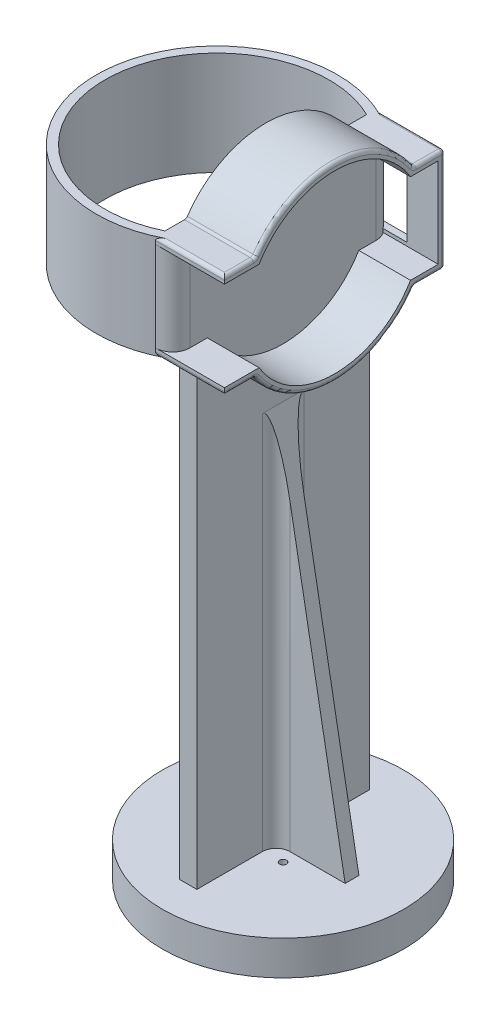
SolidWorks part; units mm, degrees
note: '?' marks a value the reader was unsure of.
ref_plane "Alzado" through (0, 0, 0) normal (0, 0, 1) x (1, 0, 0)
ref_plane "Planta" through (0, 0, 0) normal (0, 1, 0) x (1, 0, 0)
ref_plane "Vista lateral" through (0, 0, 0) normal (1, 0, 0) x (0, 0, -1)
sketch "Croquis1" plane through (0, 0, 0) normal (0, 1, 0) x (1, 0, 0)
  line L0 (0, -55) -> (0, 55) construction
  circle A0 centre (0, 0) radius 35
  point P5 (1.0317, 1.5992)
  dimension "D1" = 70
extrude "Saliente-Extruir1" add sketch "Croquis1" along normal blind 10
ref_plane "Plano1" through (0, 0, 0) normal (1, 0, 0) x (0, 0, -1)
sketch "Croquis4" plane through (0, 0, 0) normal (1, 0, 0) x (0, 0, -1)
  line L1 (-25, 10) -> (25, 10)
  line L2 (-25, 10) -> (-25, 160)
  line L3 (-25, 160) -> (25, 160)
  line L4 (25, 10) -> (25, 160)
  line L5 (35, 10) -> (-35, 10) construction
  dimension "D1" = 150
  dimension "D2" = 50
  dimension "D3" = 25
extrude "Saliente-Extruir3" add sketch "Croquis4" against normal blind 5
sketch "Croquis5" plane through (0, 0, 0) normal (1, 0, 0) x (0, 0, -1)
  line L0 (25, 160) -> (-25, 160) construction
  line L2 (-32, 145) -> (-23, 145)
  line L3 (-32, 145) -> (-32, 175)
  line L4 (-32, 175) -> (-23, 175)
  line L5 (-23, 145) -> (-23, 175)
  line L7 (23, 175) -> (32, 175)
  line L8 (23, 175) -> (23, 145)
  line L9 (23, 145) -> (32, 145)
  line L10 (32, 175) -> (32, 145)
  circle A0 centre (0, 160) radius 27.5
  line M10 (-25, 160) -> (-25, 10)
  line M12 (25, 10) -> (25, 160)
  line M13 (25, 160) -> (-25, 160)
  dimension "D1" = 55
  dimension "D2" = 30
  dimension "D3" = 9
  dimension "D4" = 32
  dimension "D5" = 15
  dimension "D6" = 30
  dimension "D7" = 9
  dimension "D8" = 15
  dimension "D9" = 32
extrude "Saliente-Extruir4" add sketch "Croquis5" along normal blind 15 and the other way blind 5 contours A0 L9 L10 L7 M12 | A0 L7 L8 M12 M13 | L9 A0 L8 M12 M13 | L2 A0 L9 L8 L5 M13 | L7 A0 L4 L5 L8 M13 | L4 A0 L5 M10 M13 | A0 L2 L5 M10 M13 | A0 L4 L3 L2 M10 | A0 L2 M10 | A0 L9 M12
sketch3d "Croquis3D1"
  line L0 (15, 173, 21.9642) -> (15, 173, 30)
  line L1 (15, 173, 30) -> (15, 147, 30)
  line L2 (15, 147, 30) -> (15, 147, 21.9642)
  line L3 (15, 147, -21.9642) -> (15, 147, -30)
  line L4 (15, 147, -30) -> (15, 173, -30)
  line L5 (15, 173, -30) -> (15, 173, -21.9642)
  line L6 (15, 173, 21.9642) -> (15, 173, 30)
  line L8 (15, 147, 30) -> (15, 147, 21.9642)
  line L9 (15, 147, -21.9642) -> (15, 147, -30)
  line L10 (15, 147, -30) -> (15, 173, -30)
  line L11 (15, 173, -30) -> (15, 173, -21.9642)
  line L12 (15, 173, 30) -> (15, 173, 32)
  line L13 (15, 145, 32) -> (15, 175, 32) construction
  line L14 (15, 173, 32) -> (15, 147, 32)
  line L15 (15, 147, 32) -> (15, 147, 30)
  line L16 (15, 145, 32) -> (15, 145, 23.0489) construction
  spline S0 degree 5 poles (15, 875.3742, 620.8936) (15, 862.2104, 487.3237) (15, 683.0793, 370.8401) (15, 504.0832, 254.3509) (15, 324.838, 137.6997) (15, 145.5929, 21.0484) (15, 145.3451, 20.8845) (15, 144.6096, 20.3812) (15, 143.9088, 19.8266) (15, 143.4553, 19.4384) (15, 142.3513, 18.433) (15, 141.3105, 17.3675) (15, 140.7119, 16.7053) (15, 139.5732, 15.3328) (15, 138.564, 13.8588) (15, 138.0925, 13.0991) (15, 137.2173, 11.54) (15, 136.4806, 9.9121) (15, 136.1479, 9.0829) (15, 135.5556, 7.3976) (15, 135.1135, 5.6665) (15, 134.9304, 4.7918) (15, 134.6411, 3.0285) (15, 134.5071, 1.2468) (15, 134.4791, 0.3536) (15, 134.5011, -1.4329) (15, 134.6794, -3.2106) (15, 134.8074, -4.095) (15, 135.1401, -5.8505) (15, 135.625, -7.5703) (15, 135.9049, -8.419) (15, 136.5382, -10.0897) (15, 137.3159, -11.6979) (15, 137.7395, -12.4846) (15, 138.6538, -14.0197) (15, 139.6972, -15.4713) (15, 140.2504, -16.1735) (15, 141.2939, -17.3806) (15, 142.4337, -18.4948) (15, 142.9519, -18.9683) (15, 143.791, -19.6898) (15, 144.66, -20.3747) (15, 144.9825, -20.6185) (15, 145.3974, -20.9162) (15, 145.823, -21.1979) (15, 145.9122, -21.2563) (15, 314.1545, -130.7469) (15, 482.3968, -240.2376) (15, 650.5497, -349.67) (15, 818.7438, -459.113) (15, 990.3967, -547.1852) knots -20.205741 -20.205741 -20.205741 -20.205741 -20.205741 -20.205741 0.020545 0.020545 0.020545 0.048685 0.048685 0.048685 0.104965 0.104965 0.104965 0.189384 0.189384 0.189384 0.273804 0.273804 0.273804 0.358223 0.358223 0.358223 0.442643 0.442643 0.442643 0.527063 0.527063 0.527063 0.611482 0.611482 0.611482 0.695902 0.695902 0.695902 0.780321 0.780321 0.780321 0.864741 0.864741 0.864741 0.931119 0.931119 0.931119 0.969357 0.969357 0.969357 0.979455 0.979455 0.979455 19.980475 19.980475 19.980475 19.980475 19.980475 19.980475 only from (15, 147, 21.9642) to (15, 147, -21.9642)
  spline S1 degree 5 poles (15, -492.3008, -546.0642) (15, -485.3034, -450.3357) (15, -320.441, -343.0914) (15, -155.6576, -235.8518) (15, 9.3748, -128.4501) (15, 174.4071, -21.0484) (15, 174.6549, -20.8845) (15, 175.3904, -20.3812) (15, 176.0912, -19.8266) (15, 176.5447, -19.4384) (15, 177.6487, -18.433) (15, 178.6895, -17.3675) (15, 179.2881, -16.7053) (15, 180.4268, -15.3328) (15, 181.436, -13.8588) (15, 181.9075, -13.0991) (15, 182.7827, -11.54) (15, 183.5194, -9.9121) (15, 183.8521, -9.0829) (15, 184.4444, -7.3976) (15, 184.8865, -5.6665) (15, 185.0696, -4.7918) (15, 185.3589, -3.0285) (15, 185.4929, -1.2468) (15, 185.5209, -0.3536) (15, 185.4989, 1.4329) (15, 185.3206, 3.2106) (15, 185.1926, 4.095) (15, 184.8599, 5.8505) (15, 184.375, 7.5703) (15, 184.0951, 8.419) (15, 183.4618, 10.0897) (15, 182.6841, 11.6979) (15, 182.2605, 12.4846) (15, 181.3462, 14.0197) (15, 180.3028, 15.4713) (15, 179.7496, 16.1735) (15, 178.7061, 17.3806) (15, 177.5663, 18.4948) (15, 177.0481, 18.9683) (15, 176.209, 19.6898) (15, 175.34, 20.3747) (15, 175.0175, 20.6185) (15, 174.6026, 20.9162) (15, 174.177, 21.1979) (15, 174.0878, 21.2563) (15, 1.8346, 133.3572) (15, -170.4187, 245.4581) (15, -342.5826, 357.5009) (14.998, -514.7904, 469.5499) (16.9078, -611.1683, 560.0445) knots -18.599717 -18.599717 -18.599717 -18.599717 -18.599717 -18.599717 0.020545 0.020545 0.020545 0.048685 0.048685 0.048685 0.104965 0.104965 0.104965 0.189384 0.189384 0.189384 0.273804 0.273804 0.273804 0.358223 0.358223 0.358223 0.442643 0.442643 0.442643 0.527063 0.527063 0.527063 0.611482 0.611482 0.611482 0.695902 0.695902 0.695902 0.780321 0.780321 0.780321 0.864741 0.864741 0.864741 0.931119 0.931119 0.931119 0.969357 0.969357 0.969357 0.979455 0.979455 0.979455 20.433704 20.433704 20.433704 20.433704 20.433704 20.433704 only from (15, 173, -21.9642) to (15, 173, 21.9642)
  spline S2 degree 5 poles (15, 147, 21.9642) (15, 146.8182, 21.8459) (15, 146.6364, 21.7276) (15, 146.4545, 21.6092) (15, 146.0237, 21.3288) (15, 145.5929, 21.0484) (15, 145.3451, 20.8845) (15, 144.6096, 20.3812) (15, 143.9088, 19.8266) (15, 143.4553, 19.4384) (15, 142.3513, 18.433) (15, 141.3105, 17.3675) (15, 140.7119, 16.7053) (15, 139.5732, 15.3328) (15, 138.564, 13.8588) (15, 138.0925, 13.0991) (15, 137.2173, 11.54) (15, 136.4806, 9.9121) (15, 136.1479, 9.0829) (15, 135.5556, 7.3976) (15, 135.1135, 5.6665) (15, 134.9304, 4.7918) (15, 134.6411, 3.0285) (15, 134.5071, 1.2468) (15, 134.4791, 0.3536) (15, 134.5011, -1.4329) (15, 134.6794, -3.2106) (15, 134.8074, -4.095) (15, 135.1401, -5.8505) (15, 135.625, -7.5703) (15, 135.9049, -8.419) (15, 136.5382, -10.0897) (15, 137.3159, -11.6979) (15, 137.7395, -12.4846) (15, 138.6538, -14.0197) (15, 139.6972, -15.4713) (15, 140.2504, -16.1735) (15, 141.2939, -17.3806) (15, 142.4337, -18.4948) (15, 142.9519, -18.9683) (15, 143.791, -19.6898) (15, 144.66, -20.3747) (15, 144.9825, -20.6185) (15, 145.3974, -20.9162) (15, 145.823, -21.1979) (15, 145.9122, -21.2563) (15, 146.1834, -21.4327) (15, 146.4545, -21.6092) (15, 146.6364, -21.7276) (15, 146.8182, -21.8459) (15, 147, -21.9642) knots 0 0 0 0 0 0 0.020545 0.020545 0.020545 0.048685 0.048685 0.048685 0.104965 0.104965 0.104965 0.189384 0.189384 0.189384 0.273804 0.273804 0.273804 0.358223 0.358223 0.358223 0.442643 0.442643 0.442643 0.527063 0.527063 0.527063 0.611482 0.611482 0.611482 0.695902 0.695902 0.695902 0.780321 0.780321 0.780321 0.864741 0.864741 0.864741 0.931119 0.931119 0.931119 0.969357 0.969357 0.969357 0.979455 0.979455 0.979455 1 1 1 1 1 1
  spline S3 degree 5 poles (15, 173, -21.9642) (15, 173.1818, -21.8459) (15, 173.3636, -21.7276) (15, 173.5455, -21.6092) (15, 173.9763, -21.3288) (15, 174.4071, -21.0484) (15, 174.6549, -20.8845) (15, 175.3904, -20.3812) (15, 176.0912, -19.8266) (15, 176.5447, -19.4384) (15, 177.6487, -18.433) (15, 178.6895, -17.3675) (15, 179.2881, -16.7053) (15, 180.4268, -15.3328) (15, 181.436, -13.8588) (15, 181.9075, -13.0991) (15, 182.7827, -11.54) (15, 183.5194, -9.9121) (15, 183.8521, -9.0829) (15, 184.4444, -7.3976) (15, 184.8865, -5.6665) (15, 185.0696, -4.7918) (15, 185.3589, -3.0285) (15, 185.4929, -1.2468) (15, 185.5209, -0.3536) (15, 185.4989, 1.4329) (15, 185.3206, 3.2106) (15, 185.1926, 4.095) (15, 184.8599, 5.8505) (15, 184.375, 7.5703) (15, 184.0951, 8.419) (15, 183.4618, 10.0897) (15, 182.6841, 11.6979) (15, 182.2605, 12.4846) (15, 181.3462, 14.0197) (15, 180.3028, 15.4713) (15, 179.7496, 16.1735) (15, 178.7061, 17.3806) (15, 177.5663, 18.4948) (15, 177.0481, 18.9683) (15, 176.209, 19.6898) (15, 175.34, 20.3747) (15, 175.0175, 20.6185) (15, 174.6026, 20.9162) (15, 174.177, 21.1979) (15, 174.0878, 21.2563) (15, 173.8166, 21.4327) (15, 173.5455, 21.6092) (15, 173.3636, 21.7276) (15, 173.1818, 21.8459) (15, 173, 21.9642) knots 0 0 0 0 0 0 0.020545 0.020545 0.020545 0.048685 0.048685 0.048685 0.104965 0.104965 0.104965 0.189384 0.189384 0.189384 0.273804 0.273804 0.273804 0.358223 0.358223 0.358223 0.442643 0.442643 0.442643 0.527063 0.527063 0.527063 0.611482 0.611482 0.611482 0.695902 0.695902 0.695902 0.780321 0.780321 0.780321 0.864741 0.864741 0.864741 0.931119 0.931119 0.931119 0.969357 0.969357 0.969357 0.979455 0.979455 0.979455 1 1 1 1 1 1
  dimension "D1" = 2
extrude "Cortar-Extruir2" cut sketch "Croquis3D1" along direction (1, 0, 0) on the side of the normal blind 15 contours L6 L12 L14 L15 L8 S2 L9 L10 L11 S3
sketch "Croquis6" plane through (0, 145, 0) normal (0, -1, 0) x (1, 0, 0)
  line L0 (-5, 32) -> (-5, 29.2447)
  line L1 (-5, 32) -> (-5, 25) construction
  line L2 (-5, -29.2447) -> (-5, -32)
  line L3 (-5, -25) -> (-5, -32) construction
  arc A0 (-5, 32) -> (-5, -32) centre (-19.1774, 0) ccw
  arc A1 (-5, 29.2447) -> (-5, -29.2447) centre (-19.1774, 0) ccw
  dimension "D1" = 70
  dimension "D2" = 65
extrude "Saliente-Extruir5" add sketch "Croquis6" against normal blind 30
sketch "Croquis7" plane through (0, 0, -32) normal (0, 0, -1) x (-1, 0, 0)
  line L0 (0, 55) -> (0, -55) construction
  line L1 (0, 172) -> (-6, 172)
  line L2 (0, 172) -> (0, 148)
  line L3 (0, 148) -> (-6, 148)
  line L4 (-6, 172) -> (-6, 148)
  line L5 (5, 175) -> (-15, 175) construction
  line L6 (5, 145) -> (-15, 145) construction
  dimension "D1" = 6
  dimension "D2" = 3
  dimension "D3" = 3
extrude "Cortar-Extruir3" cut sketch "Croquis7" against normal up to next
fillet "Redondeo1" radius 5 2 edges at (0, 160, -32)
fillet "Redondeo2" radius 1 15 edges at (7.5, 145, -23.0489) (7.5, 145, 23.0489) (5, 175, 23.0489) (5, 175, -23.0489) (5, 175, -32) (5, 145, -32) (15, 175, -27.5244) (15, 145, -27.5244) (15, 132.5, 0) (5, 145, 32) (15, 145, 27.5244) (15, 175, 27.5244) (15, 187.5, 0) (5, 175, 32) (15, 160, -32)
ref_plane "Plano2" through (0, 0, 0) normal (0, 0, 1) x (1, 0, 0)
sketch "Croquis8" plane through (0, 0, 0) normal (0, 0, 1) x (1, 0, 0)
  line L0 (0, 120) -> (20, 10)
  line L1 (0, 145) -> (0, 10) construction
  line L3 (35, 10) -> (-35, 10) construction
  dimension "D1" = 20
  dimension "D2" = 110
rib "Nervio1" sketch "Croquis8" sketch "Croquis8" thickness 4 extrusion direction parallel to sketch draft on no parameters "D1"=4
ref_plane "Plano3" through (-2.5, 0, 0) normal (1, 0, 0) x (0, 0, -1)
ref_plane "Plano4" through (-2.5, 0, 0) normal (-1, 0, 0) x (0, 0, 1)
ref_plane "Plano5" through (0, 0, 0) normal (0, 0, 1) x (1, 0, 0)
ref_axis "Eje1" through (0, 245.7147, 0) along (0, -1, 0)?
sketch "Croquis11" plane through (0, 0, 0) normal (0, -1, 0) x (1, 0, 0)
  line L0 (0, 0) -> (0, 8)
  line L1 (0, 0) -> (5.6569, 5.6569)
  circle A9 centre (0, 0) radius 8
  circle A11 centre (5.6569, 5.6569) radius 1
  circle A12 centre (5.6569, -5.6569) radius 1
  circle A13 centre (-5.6569, -5.6569) radius 1
  circle A14 centre (-5.6569, 5.6569) radius 1
  point P21 (0, 0)
  dimension "D1" = 16
  dimension "D3" = 45
  dimension "D4" = 16
  dimension "2" = 2
  dimension "D5" = 5.6569
extrude "Cortar-Extruir7" cut sketch "Croquis11" against normal blind 10 contours A9 A14 | A9 A14 | A9 A13 | A9 A13 | A9 A12 | A9 A12 | L1 A11 A9
ref_plane "Plano6" through (-5, 10, 6.4109) normal (-0.754, 0, 0.6569) x (0.6569, 0, 0.754)
sketch "Croquis13" plane through (0, 10, 0) normal (0, 1, 0) x (1, 0, 0)
  circle A0 centre (-5.6569, 5.6569) radius 3
  circle A1 centre (-5.6569, -5.6569) radius 3
  dimension "D1" = 6
  dimension "D2" = 6
extrude "Cortar-Extruir8" cut sketch "Croquis13" along normal blind 3
sketch "Croquis14" plane through (0, 0, 0) normal (0, -1, 0) x (1, 0, 0)
  circle A0 centre (0, 0) radius 11.5
  dimension "D1" = 23
extrude "Cortar-Extruir9" cut sketch "Croquis14" against normal blind 2
mirror "Simetría1" about plane through (-2.5, 0, 0) normal (-1, 0, 0) of "Nervio1"
fillet "Redondeo3" radius 4 4 edges at (-5, 65, -2) (0, 65, -2) (-5, 65, 2) (0, 65, 2)
